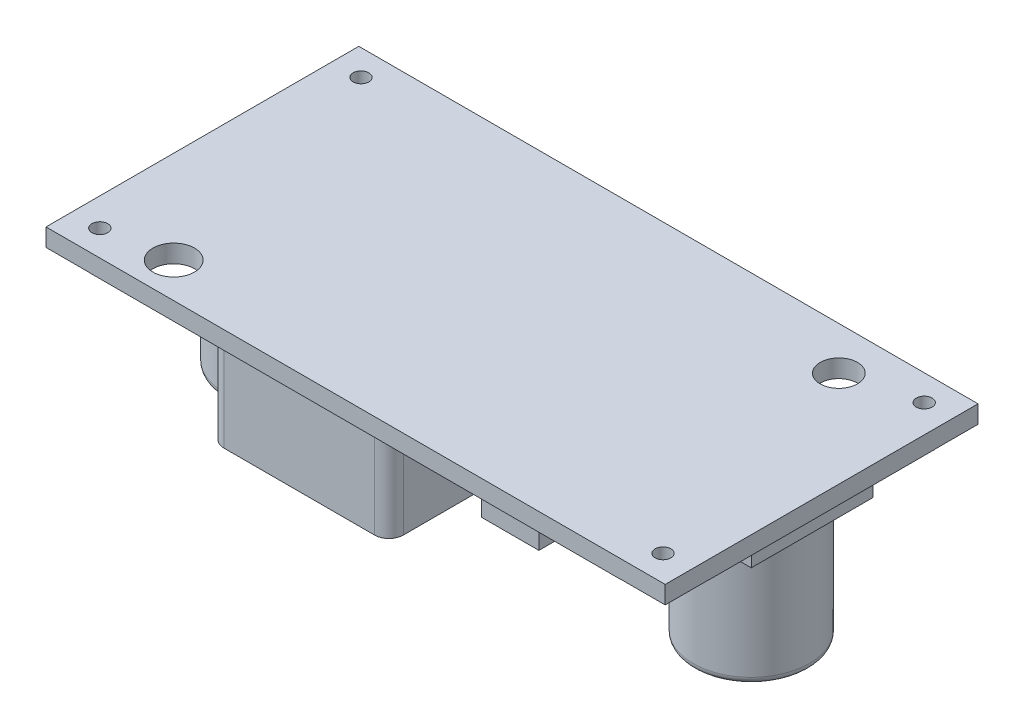
SolidWorks part; units mm, degrees
ref_plane "Front Plane" through (0, 0, 0) normal (0, 0, 1) x (1, 0, 0)
ref_plane "Top Plane" through (0, 0, 0) normal (0, 1, 0) x (1, 0, 0)
ref_plane "Right Plane" through (0, 0, 0) normal (1, 0, 0) x (0, 0, -1)
sketch "Sketch1" plane through (0, 0, 0) normal (0, 1, 0) x (1, 0, 0)
  line L1 (-21.575, -10.9) -> (21.575, -10.9)
  line L2 (-21.575, -10.9) -> (-21.575, 10.9)
  line L3 (-21.575, 10.9) -> (21.575, 10.9)
  line L4 (21.575, -10.9) -> (21.575, 10.9)
  line L5 (-21.575, -10.9) -> (21.575, 10.9) construction
  line L6 (-21.575, 10.9) -> (21.575, -10.9) construction
  point P0 (0, 0)
  dimension "D1" = 21.8
  dimension "D2" = 43.15
extrude "Boss-Extrude1" add sketch "Sketch1" along normal blind 1.25
sketch "Sketch2" plane through (0, 1.25, 0) normal (0, 1, 0) x (1, 0, 0)
  line L4 (21.575, 10.9) -> (-21.575, 10.9) construction
  line L5 (21.575, -10.9) -> (21.575, 10.9) construction
  line L6 (-21.575, -10.9) -> (21.575, -10.9) construction
  line L7 (-21.575, 10.9) -> (-21.575, -10.9) construction
  circle A0 centre (19.625, 9.1) radius 0.55
  circle A1 centre (19.625, -9.1) radius 0.55
  circle A2 centre (-19.625, 9.1) radius 0.55
  circle A3 centre (-19.625, -9.1) radius 0.55
  point P16 (20.175, 9.1)
  point P17 (19.625, 9.65)
  point P18 (-20.175, 9.1)
  point P19 (-19.625, -9.65)
  dimension "D3" = 1.1
  dimension "D1" = 1.4
  dimension "D2" = 1.25
  dimension "D4" = 1.4
  dimension "D5" = 1.25
extrude "Cut-Extrude1" cut sketch "Sketch2" against normal through all
sketch "Sketch3" plane through (0, 1.25, 0) normal (0, 1, 0) x (1, 0, 0)
  line L1 (-21.575, 10.9) -> (-21.575, -10.9) construction
  line L3 (21.575, 10.9) -> (-21.575, 10.9) construction
  line L4 (-21.575, -10.9) -> (21.575, -10.9) construction
  circle A0 centre (14.875, 7.9) radius 1.3
  circle A1 centre (-15.125, -8.45) radius 1.45
  point P4 (-16.575, -8.45)
  point P7 (16.175, 7.9)
  point P10 (14.875, 9.2)
  point P11 (-15.125, -9.9)
  dimension "D1" = 2.6
  dimension "D2" = 2.9
  dimension "D3" = 30
  dimension "D4" = 5
  dimension "D5" = 1.7
  dimension "D6" = 1
extrude "Cut-Extrude2" cut sketch "Sketch3" against normal through all
sketch "Sketch4" plane through (0, 0, 0) normal (0, -1, 0) x (1, 0, 0)
  line L1 (21.575, -10.9) -> (18.575, -10.9)
  line L2 (21.575, -10.9) -> (21.575, -7.9)
  line L3 (21.575, -7.9) -> (18.575, -7.9)
  line L4 (18.575, -10.9) -> (18.575, -7.9)
  line L5 (21.575, 10.9) -> (18.575, 10.9)
  line L6 (21.575, 10.9) -> (21.575, 7.9)
  line L7 (21.575, 7.9) -> (18.575, 7.9)
  line L8 (18.575, 10.9) -> (18.575, 7.9)
  line L9 (-21.575, 10.9) -> (-18.575, 10.9)
  line L10 (-21.575, 10.9) -> (-21.575, 7.9)
  line L11 (-21.575, 7.9) -> (-18.575, 7.9)
  line L12 (-18.575, 10.9) -> (-18.575, 7.9)
  line L13 (-21.575, -10.9) -> (-18.575, -10.9)
  line L14 (-21.575, -10.9) -> (-21.575, -7.9)
  line L15 (-21.575, -7.9) -> (-18.575, -7.9)
  line L16 (-18.575, -10.9) -> (-18.575, -7.9)
  dimension "D1" = 3
extrude "Cut-Extrude3" cut sketch "Sketch4" against normal blind 0.01
sketch "Sketch5" plane through (0, 0, 0) normal (0, -1, 0) x (1, 0, 0)
  line L0 (20.7466, -6.7043) -> (18.394, -6.7043) construction
  line L1 (20.7466, 7.55) -> (18.394, 7.55) construction
  line L2 (-17.7724, -6.7043) -> (-20.4941, -6.7043) construction
  line L3 (-17.7724, 7.55) -> (-20.4941, 7.55) construction
  text T0 "IN+" font "Century Gothic" height 1
  text T1 "IN-" font "Century Gothic" height 1
  text T2 "OUT+" font "Century Gothic" height 1
  text T3 "OUT-" font "Century Gothic" height 1
extrude "Cut-Extrude4" cut sketch "Sketch5" against normal blind 0.01
sketch "Sketch6" plane through (0, 0, 0) normal (0, -1, 0) x (1, 0, 0)
  line L0 (-18.575, 10.9) -> (18.575, 10.9) construction
  line L1 (12.075, 3.9) -> (20.575, 3.9)
  line L2 (12.075, 3.9) -> (12.075, -4.6)
  line L3 (12.075, -4.6) -> (20.575, -4.6)
  line L4 (20.575, 3.9) -> (20.575, -4.6)
  line L5 (12.075, 3.9) -> (20.575, -4.6) construction
  line L6 (12.075, -4.6) -> (20.575, 3.9) construction
  line L7 (-20.575, 3.9) -> (-12.075, 3.9)
  line L8 (-20.575, 3.9) -> (-20.575, -4.6)
  line L9 (-20.575, -4.6) -> (-12.075, -4.6)
  line L10 (-12.075, 3.9) -> (-12.075, -4.6)
  line L11 (-20.575, 3.9) -> (-12.075, -4.6) construction
  line L12 (-20.575, -4.6) -> (-12.075, 3.9) construction
  line L13 (-21.575, -7.9) -> (-21.575, 7.9) construction
  line L14 (21.575, 7.9) -> (21.575, -7.9) construction
  point P0 (16.325, -0.35)
  point P5 (-16.325, -0.35)
  dimension "D1" = 8.5
  dimension "D2" = 7
  dimension "D3" = 1
  dimension "D4" = 1
extrude "Boss-Extrude2" add sketch "Sketch6" along normal blind 1.75
sketch "Sketch7" plane through (0, -1.75, 0) normal (0, -1, 0) x (1, 0, 0)
  line L0 (20.575, 3.9) -> (12.075, 3.9) construction
  line L1 (-12.075, -4.6) -> (-12.075, 3.9) construction
  line L2 (-12.075, 3.9) -> (-20.575, 3.9) construction
  line L3 (12.075, 3.9) -> (12.075, -4.6) construction
  circle A0 centre (-16.325, -0.35) radius 4.05
  circle A1 centre (16.325, -0.35) radius 4.05
  point P6 (16.325, 3.9)
  point P9 (-12.075, -0.35)
  point P12 (-16.325, 3.9)
  point P15 (12.075, -0.35)
  dimension "D1" = 8.1
extrude "Boss-Extrude3" add sketch "Sketch7" along normal blind 8.5
fillet "Fillet1" radius 0.5 2 edges at (16.325, -10.25, -4.4) (-16.325, -10.25, -4.4)
sketch "Sketch8" plane through (0, 0, 0) normal (0, -1, 0) x (1, 0, 0)
  line L0 (-18.575, 10.9) -> (18.575, 10.9) construction
  line L1 (-11.375, 9.7) -> (1.125, 9.7)
  line L2 (-11.375, 9.7) -> (-11.375, -2.8)
  line L3 (-11.375, -2.8) -> (1.125, -2.8)
  line L4 (1.125, 9.7) -> (1.125, -2.8)
  line L5 (-21.575, -7.9) -> (-21.575, 7.9) construction
  dimension "D1" = 12.5
  dimension "D2" = 1.2
  dimension "D3" = 10.2
extrude "Boss-Extrude4" add sketch "Sketch8" along normal blind 7.1
fillet "Fillet2" radius 1 4 edges at (-11.375, -3.55, -2.8) (1.125, -3.55, -2.8) (1.125, -3.55, 9.7) (-11.375, -3.55, 9.7)
sketch "Sketch9" plane through (0, 0, 0) normal (0, -1, 0) x (1, 0, 0)
  line L0 (-10.225, -4.5) -> (-10.225, -5.2)
  line L1 (-10.925, -4.5) -> (-10.225, -4.5)
  line L2 (-10.925, -4.5) -> (-10.925, -9.5)
  line L3 (-10.925, -9.5) -> (-1.425, -9.5)
  line L4 (-1.425, -4.5) -> (-1.425, -9.5)
  line L5 (-10.225, -5.2) -> (-2.125, -5.2)
  line L6 (-2.125, -5.2) -> (-2.125, -4.5)
  line L7 (-2.125, -4.5) -> (-1.425, -4.5)
  line L8 (-6.175, -5.2) -> (-6.175, -9.5) construction
  line L9 (18.575, -10.9) -> (-18.575, -10.9) construction
  line L10 (-21.575, -7.9) -> (-21.575, 7.9) construction
  dimension "D1" = 9.5
  dimension "D2" = 5
  dimension "D3" = 4.3
  dimension "D4" = 1.4
  dimension "D5" = 10.65
extrude "Boss-Extrude5" add sketch "Sketch9" along normal blind 10
sketch "Sketch10" plane through (0, 0, 0) normal (0, -1, 0) x (1, 0, 0)
  line L0 (21.575, 7.9) -> (21.575, -7.9) construction
  line L1 (7.575, 9.7) -> (11.575, 9.7)
  line L2 (7.575, 9.7) -> (7.575, 7.2)
  line L3 (7.575, 7.2) -> (11.575, 7.2)
  line L4 (11.575, 9.7) -> (11.575, 7.2)
  line L5 (-18.575, 10.9) -> (18.575, 10.9) construction
  dimension "D1" = 4
  dimension "D2" = 2.5
  dimension "D3" = 10
  dimension "D4" = 1.2
extrude "Boss-Extrude6" add sketch "Sketch10" along normal blind 2.3
sketch "Sketch11" plane through (0, 0, 0) normal (0, -1, 0) x (1, 0, 0)
  line L0 (1.125, -1.8) -> (1.125, 8.7) construction
  line L1 (1.625, 0.6) -> (11.625, 0.6)
  line L2 (1.625, 0.6) -> (1.625, -7.8)
  line L3 (1.625, -7.8) -> (11.625, -7.8)
  line L4 (11.625, 0.6) -> (11.625, -7.8)
  line L5 (18.575, -10.9) -> (-18.575, -10.9) construction
  dimension "D1" = 8.4
  dimension "D2" = 10
  dimension "D3" = 0.5
  dimension "D4" = 3.1
extrude "Boss-Extrude7" add sketch "Sketch11" along normal blind 4.3
chamfer "Chamfer1" distance 2 angle 20 2 edges at (6.625, -4.3, 0.6) (6.625, -4.3, -7.8) first distance on face at (6.625, -2.15, 0.6) first distance on face at (6.625, -2.15, -7.8)
sketch "Sketch12" plane through (0, 0, 0) normal (0, -1, 0) x (1, 0, 0)
  line L0 (11.625, -7.8) -> (11.625, 0.6) construction
  line L1 (1.625, -7.8) -> (11.625, -7.8)
  line L2 (1.625, -7.8) -> (1.625, -9.3)
  line L3 (1.625, -9.3) -> (11.625, -9.3)
  line L4 (11.625, -7.8) -> (11.625, -9.3)
  dimension "D1" = 1.5
extrude "Boss-Extrude8" add sketch "Sketch12" along normal blind 1
sketch "Sketch13" plane through (0, 0, 0) normal (0, -1, 0) x (1, 0, 0)
  line L0 (11.625, 0.6) -> (1.625, 0.6) construction
  line L1 (2.375, 5.6) -> (3.375, 5.6)
  line L2 (2.375, 5.6) -> (2.375, 0.6)
  line L3 (2.375, 0.6) -> (3.375, 0.6)
  line L4 (3.375, 5.6) -> (3.375, 0.6)
  line L5 (1.625, -0.1279) -> (1.625, 0.6) construction
  dimension "D1" = 0.75
  dimension "D2" = 1
  dimension "D3" = 5
extrude "Boss-Extrude9" add sketch "Sketch13" along normal blind 1
pattern_linear "LPattern1" count 5 spacing 1.9 along (1, 0, 0) of "Boss-Extrude9"
sketch "Sketch14" plane through (0, -10, 0) normal (0, -1, 0) x (1, 0, 0)
  line L0 (-10.925, -9.5) -> (-1.425, -9.5) construction
  line L1 (-1.425, -9.5) -> (-1.425, -4.5) construction
  circle A0 centre (-2.575, -8.2) radius 1.15
  dimension "D1" = 2.3
  dimension "D2" = 1.3
extrude "Boss-Extrude10" add sketch "Sketch14" along normal blind 1.6
